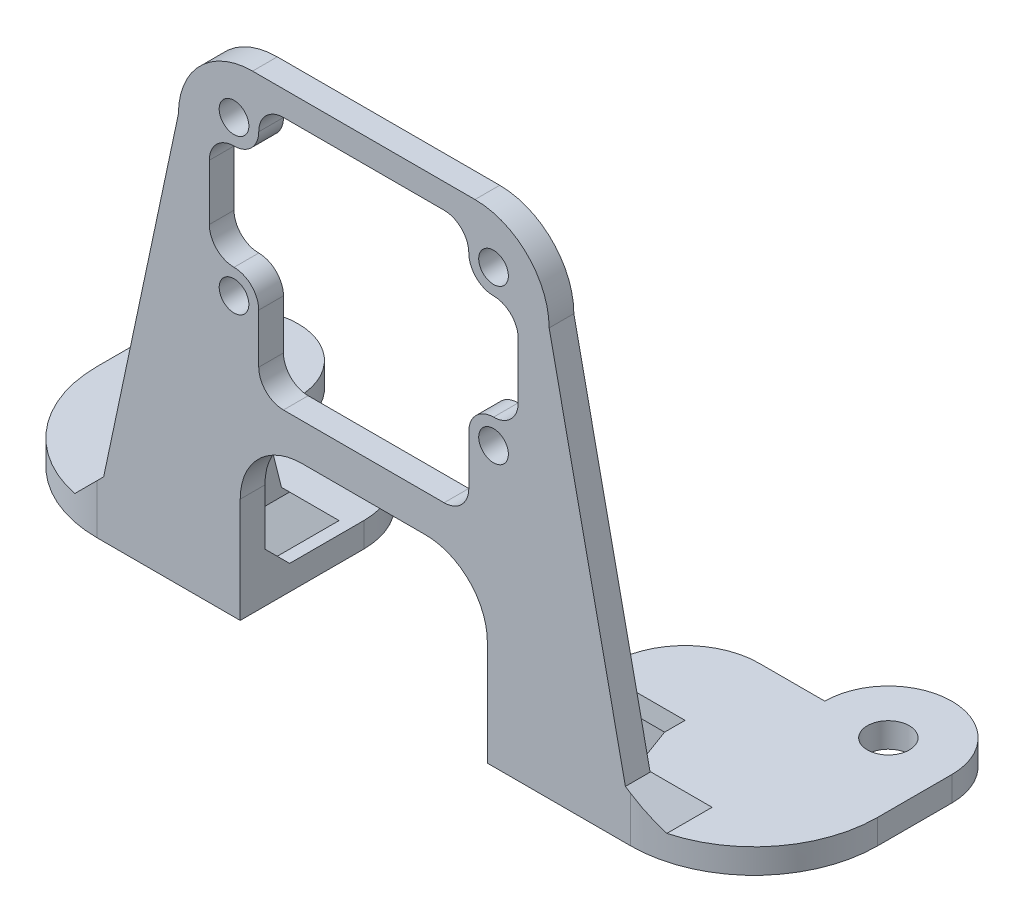
SolidWorks part; units mm, degrees
ref_plane "Front Plane" through (0, 0, 0) normal (0, 0, 1) x (1, 0, 0)
ref_plane "Top Plane" through (0, 0, 0) normal (0, 1, 0) x (1, 0, 0)
ref_plane "Right Plane" through (0, 0, 0) normal (1, 0, 0) x (0, 0, -1)
sketch "Sketch1" plane through (0, 0, 0) normal (0, 1, 0) x (1, 0, 0)
  line L0 (-26.45, 0) -> (26.45, 0) construction
  line L1 (0, 0) -> (0, -3) construction
  line L2 (0, -3) -> (0, 53.7) construction
  line L3 (-21.3106, 0) -> (21.3106, 0)
  line L4 (-10, -3) -> (10, -3)
  line L5 (-10, -3) -> (-10, -10.5262)
  line L6 (10, -3) -> (10, -10.5262)
  line L7 (-10, 0) -> (-10, -11.3) construction
  line L8 (10, 0) -> (10, -11.3) construction
  line L9 (0, 0) -> (0, -11.3) construction
  line L10 (-21.3106, -3) -> (21.3106, -3) construction
  line L11 (-31.5894, 0) -> (-31.5894, -16)
  line L12 (-31.5894, -16) -> (-10, -16)
  line L13 (31.5894, 0) -> (31.5894, -16)
  line L14 (0, -11.3) -> (0, -16) construction
  line L15 (-10, -10.5262) -> (-10, -16)
  line L16 (10, -10.5262) -> (10, -16)
  line L17 (10, -16) -> (31.5894, -16)
  circle A0 centre (-26.45, 0) radius 1.7
  circle A1 centre (26.45, 0) radius 1.7
  arc A2 (31.5894, -3.1077) -> (-31.5894, -3.1077) centre (0, 53.7) ccw construction
  arc A3 (-21.3106, 0) -> (-31.5894, 0) centre (-26.45, 0) ccw
  arc A4 (31.5894, 0) -> (21.3106, 0) centre (26.45, 0) ccw
  arc A7 (-10, -10.5262) -> (10, -10.5262) centre (0, 53.7) ccw construction
  arc A8 (31.5894, -3.1077) -> (-31.5894, -3.1077) centre (0, 53.7) ccw construction
  point P4 (0, 0)
  dimension "D1" = 3
  dimension "D2" = 10
  dimension "D3" = 10
extrude "Boss-Extrude1" add sketch "Sketch1" along normal blind 2
sketch "Sketch2" plane through (0, 2, 0) normal (0, 1, 0) x (1, 0, 0)
  line L0 (-10, -16) -> (10, -16) construction
  line L1 (-15, -16) -> (15, -16)
  line L2 (10, -16) -> (31.5894, -16) construction
  line L3 (-15, -14) -> (15, -14)
  line L4 (15, -14) -> (15, -16)
  line L5 (-15, -14) -> (-15, -16)
  point P9 (0, -16)
  dimension "D1" = 2
extrude "Boss-Extrude2" add sketch "Sketch2" along normal blind 35
sketch "Sketch4" plane through (0, 0, 16) normal (0, 0, 1) x (1, 0, 0)
  line L0 (0, 2) -> (0, 37) construction
  line L1 (-10, 2) -> (10, 2) construction
  line L2 (-15, 37) -> (15, 37) construction
  line L3 (-8.5, 37) -> (8.5, 37) construction
  line L5 (-12.5, 33) -> (-12.5, 24.5)
  line L6 (-8.5, 20.5) -> (8.5, 20.5)
  line L7 (12.5, 24.5) -> (12.5, 33)
  line L8 (-10.5, 35) -> (10.5, 35) construction
  line L9 (10.5, 12.2) -> (10.5, 35) construction
  line L10 (-10.5, 22.5) -> (8.5, 22.5) construction
  line L11 (-10.5, 35) -> (-10.5, 22.5) construction
  line L12 (-10.5, 33) -> (-12.5, 33)
  line L13 (10.5, 33) -> (12.5, 33)
  line L14 (10.5, 24.5) -> (12.5, 24.5)
  line L15 (8.5, 22.5) -> (8.5, 20.5)
  line L16 (-8.5, 22.5) -> (-8.5, 20.5)
  line L17 (-10.5, 24.5) -> (-12.5, 24.5)
  line L18 (-12.5, 37) -> (12.5, 37) construction
  line L19 (-12.5, 37) -> (-12.5, 20.5) construction
  line L20 (10.5, 22.5) -> (10.5, 35) construction
  line L21 (12.5, 20.5) -> (12.5, 37) construction
  line L22 (-12.5, 20.5) -> (12.5, 20.5) construction
  line L23 (-10.5, 22.5) -> (10.5, 22.5) construction
  line L27 (-8.5, 37) -> (8.5, 37)
  line L31 (-8.5, 35) -> (-8.5, 37)
  line L32 (8.5, 37) -> (8.5, 35)
  arc A4 (-10.5, 33) -> (-8.5, 35) centre (-10.5, 35) ccw
  arc A5 (8.5, 35) -> (10.5, 33) centre (10.5, 35) ccw
  arc A6 (10.5, 24.5) -> (8.5, 22.5) centre (10.5, 22.5) ccw
  arc A7 (-8.5, 22.5) -> (-10.5, 24.5) centre (-10.5, 22.5) ccw
  point P9 (0, 37)
  dimension "D1" = 2
  dimension "D2" = 2
extrude "Cut-Extrude1" cut sketch "Sketch4" against normal up to vertex (2 mm away)
sketch "Sketch5" plane through (0, 0, 16) normal (0, 0, 1) x (1, 0, 0)
  line L0 (-10.5, 22.5) -> (10.5, 22.5) construction
  line L1 (0, 22.5) -> (0, 5) construction
  line L3 (-8.5, 20.5) -> (8.5, 20.5)
  line L4 (-8.5, 20.5) -> (-8.5, 5)
  line L5 (-8.5, 5) -> (8.5, 5)
  line L6 (8.5, 20.5) -> (8.5, 5)
extrude "Cut-Extrude2" cut sketch "Sketch5" against normal up to vertex (2 mm away)
sketch "Sketch6" plane through (0, 0, 16) normal (0, 0, 1) x (1, 0, 0)
  circle A0 centre (-10.5, 35) radius 1.2
  circle A1 centre (10.5, 35) radius 1.2
  circle A2 centre (-10.5, 22.5) radius 1.2
  circle A3 centre (10.5, 22.5) radius 1.2
extrude "Cut-Extrude3" cut sketch "Sketch6" against normal up to vertex (2 mm away)
sketch "Sketch7" plane through (0, 0, 16) normal (0, 0, 1) x (1, 0, 0)
  line L0 (-10.5, 35) -> (-10.5, 29) construction
  line L1 (-15, 37) -> (-15, 2) construction
  line L2 (-15, 39) -> (15, 39)
  line L3 (-15, 39) -> (-15, 37)
  line L4 (-15, 37) -> (15, 37)
  line L5 (15, 39) -> (15, 37)
extrude "Boss-Extrude4" add sketch "Sketch7" against normal up to vertex
sketch "Sketch8" plane through (0, 2, 0) normal (0, 1, 0) x (1, 0, 0)
  line L0 (21.3106, 0) -> (-21.3106, 0) construction
  line L1 (-10, -3) -> (10, -3)
  line L2 (-10, -3) -> (-10, 0)
  line L3 (-10, 0) -> (10, 0)
  line L4 (10, -3) -> (10, 0)
extrude "Cut-Extrude4" cut sketch "Sketch8" against normal up to vertex (2 mm away)
sketch "Sketch9" plane through (0, 0, 16) normal (0, 0, 1) x (1, 0, 0)
  line L0 (-10, 2) -> (10, 2) construction
  line L1 (-8.5, 5) -> (8.5, 5)
  line L2 (-8.5, 5) -> (-8.5, 2)
  line L3 (-8.5, 2) -> (8.5, 2)
  line L4 (8.5, 5) -> (8.5, 2)
extrude "Cut-Extrude5" cut sketch "Sketch9" against normal up to vertex (2 mm away)
sketch "Sketch10" plane through (0, 0, 14) normal (0, 0, -1) x (-1, 0, 0)
  line L1 (15, 2) -> (13, 2)
  line L2 (15, 2) -> (15, 22)
  line L3 (15, 22) -> (13, 22)
  line L4 (13, 2) -> (13, 22)
  line L5 (-15, 2) -> (-13, 2)
  line L6 (-15, 2) -> (-15, 22)
  line L7 (-15, 22) -> (-13, 22)
  line L8 (-13, 2) -> (-13, 22)
extrude "Boss-Extrude5" add sketch "Sketch10" along normal blind 5
sketch "Sketch11" plane through (-15, 0, 0) normal (-1, 0, 0) x (0, 0, 1)
  line L0 (14, 22) -> (9, 2)
  line L1 (9, 2) -> (9, 22)
  line L2 (9, 22) -> (14, 22)
extrude "Cut-Extrude6" cut sketch "Sketch11" against normal up to vertex
fillet "Fillet1" radius 10 2 edges at (31.5894, 1, 16) (-31.5894, 1, 16)
sketch "Sketch12" plane through (0, 0, 16) normal (0, 0, 1) x (1, 0, 0)
  line L0 (-10, 2) -> (-10, 20.5635)
  line L1 (-10, 20.5635) -> (10, 20.5635)
  line L2 (10, 2) -> (10, 20.5635)
  line L3 (-10, 2) -> (10, 2)
extrude "Cut-Extrude7" cut sketch "Sketch12" against normal up to vertex (2 mm away)
fillet "Fillet2" radius 2 2 edges at (8.5, 20.5635, 15) (-8.5, 20.5635, 15)
sketch "Sketch13" plane through (0, 0, 16) normal (0, 0, 1) x (1, 0, 0)
  line L0 (-15, 2) -> (-15, 33)
  line L1 (-15, 39) -> (-15, 2) construction
  line L2 (-15, 33) -> (-21.5894, 2)
  line L3 (-21.5894, 2) -> (-15, 2)
  line L4 (21.5894, 2) -> (15, 2)
  line L5 (15, 2) -> (15, 33)
  line L6 (15, 33) -> (21.5894, 2)
  line L7 (-10.5, 33) -> (-12.5, 33) construction
  line L8 (12.5, 33) -> (10.5, 33) construction
  point P11 (0, 0)
  point P14 (-15, 32.7099)
  point P17 (0, 0)
extrude "Boss-Extrude6" add sketch "Sketch13" against normal up to vertex
sketch "Sketch14" plane through (0, 0, 16) normal (0, 0, 1) x (1, 0, 0)
  line L0 (10.5, 22.5) -> (10.5, 16.5) construction
  line L1 (10.5, 16.5) -> (-10.5, 16.5)
  line L2 (-10.5, 16.5) -> (-10.5, 5)
  line L3 (-21.5894, 0) -> (-10, 0) construction
  line L4 (-10.5, 5) -> (10.5, 5)
  line L5 (10.5, 5) -> (10.5, 16.5)
  dimension "D1" = 5
extrude "Boss-Extrude7" add sketch "Sketch14" against normal up to vertex
sketch "Sketch15" plane through (0, 0, 16) normal (0, 0, 1) x (1, 0, 0)
  line L0 (-8.5, 22.5) -> (-8.5, 16.5)
  line L1 (10, 16.5) -> (-10, 16.5) construction
  line L2 (-8.5, 16.5) -> (-10, 16.5)
  line L3 (-10, 16.5) -> (-10, 20.5635)
  line L4 (8.5, 22.5) -> (8.5, 16.5)
  line L5 (8.5, 16.5) -> (10, 16.5)
  line L6 (10, 16.5) -> (10, 20.5635)
  arc A0 (-10, 20.5635) -> (-8.5, 22.5) centre (-10.5, 22.5) ccw construction
  arc A1 (-10, 20.5635) -> (-8.5, 22.5) centre (-10.5, 22.5) ccw
  arc A2 (8.5, 22.5) -> (10, 20.5635) centre (10.5, 22.5) ccw construction
  arc A3 (8.5, 22.5) -> (10, 20.5635) centre (10.5, 22.5) ccw
extrude "Boss-Extrude8" add sketch "Sketch15" against normal up to vertex
fillet "Fillet3" radius 2 8 edges at (-8.5, 16.5, 15) (8.5, 16.5, 15) (12.5, 24.5, 15) (-12.5, 24.5, 15) (12.5, 33, 15) (8.5, 37, 15) (-8.5, 37, 15) (-12.5, 33, 15)
fillet "Fillet4" radius 6 2 edges at (15, 39, 15) (-15, 39, 15)
sketch "Sketch16" plane through (0, 0, 16) normal (0, 0, 1) x (1, 0, 0)
  line L0 (-10.5, 22.5) -> (-10.5, 13.5) construction
  line L2 (-10, 5) -> (10, 5)
  line L3 (-10, 5) -> (-10, 13.5)
  line L4 (-10, 13.5) -> (10, 13.5)
  line L5 (10, 5) -> (10, 13.5)
extrude "Cut-Extrude8" cut sketch "Sketch16" against normal up to vertex (2 mm away)
fillet "Fillet5" radius 5 2 edges at (10, 13.5, 15) (-10, 13.5, 15)
chamfer "Chamfer1" distance 2 angle 45 12 edges at (21.5894, 2, 15) (18.2947, 2, 14) (15, 2, 11.5) (14, 2, 9) (13, 2, 11.5) (11.5, 2, 14) (-11.5, 2, 14) (-13, 2, 11.5) (-14, 2, 9) (-21.5894, 2, 15) (-15, 2, 11.5) (-18.2947, 2, 14)
chamfer "Chamfer2" distance 1 angle 45 4 edges at (16, 3, 13) (-16, 3, 13) (-15, 13, 14) (15, 13, 14)
fillet "Fillet6" radius 6 2 edges at (-10, 1, 0) (10, 1, 0)
